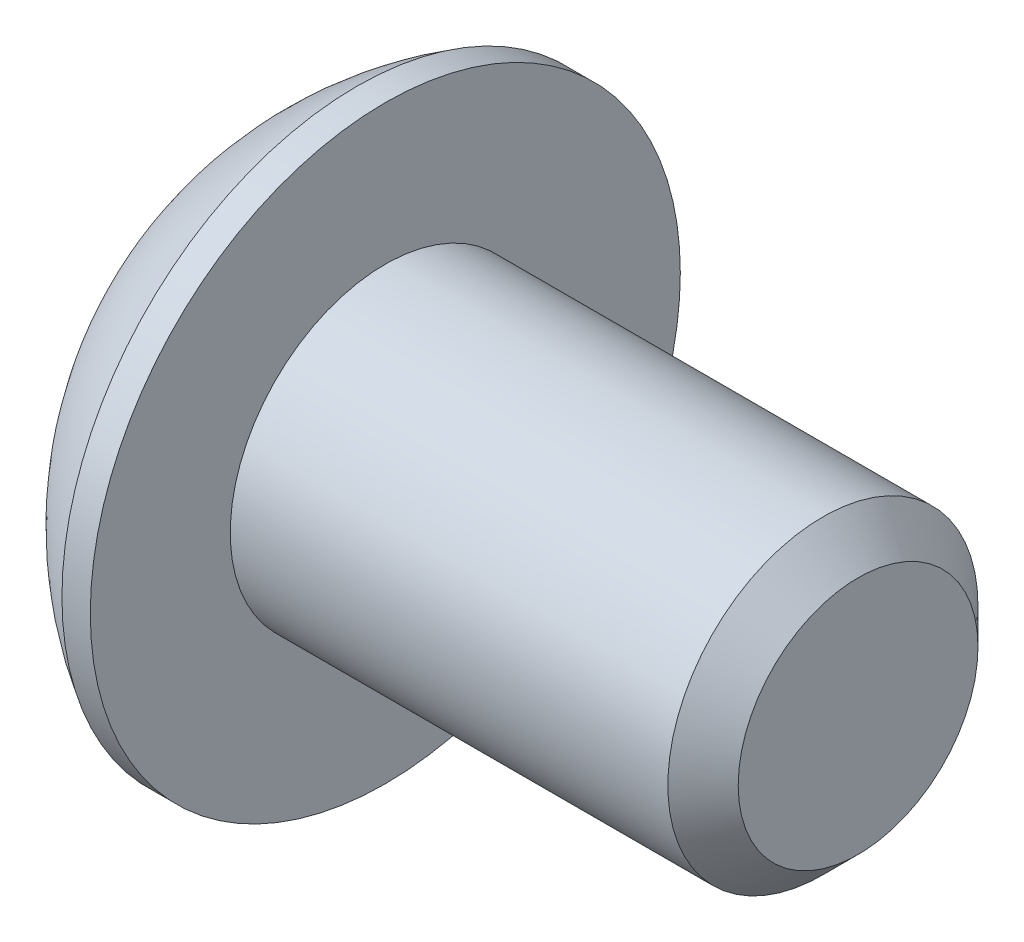
SolidWorks part; units mm, degrees
material "Cast Carbon Steel"
ref_plane "Front Plane" through (0, 0, 0) normal (0, 0, 1) x (1, 0, 0)
ref_plane "Top Plane" through (0, 0, 0) normal (0, 1, 0) x (1, 0, 0)
ref_plane "Right Plane" through (0, 0, 0) normal (1, 0, 0) x (0, 0, -1)
sketch "Sketch1" plane through (0, 0, 0) normal (0, 0, 1) x (1, 0, 0)
  line L0 (4.2799, 0) -> (-4.2799, 0) construction
  line L1 (4.2799, 0) -> (-4.2799, 0)
  line L14 (4.2799, 0) -> (4.2799, 2.0828)
  line L16 (4.2799, 2.0828) -> (-2.0701, 2.0828)
  line L17 (-2.0701, 2.0828) -> (-2.0701, 3.9624)
  line L18 (-2.0701, 3.9624) -> (-2.4511, 3.9624)
  line L19 (-4.2799, 1.9812) -> (-4.2799, 0)
  arc A1 (-2.4511, 3.9624) -> (-4.2799, 1.9812) centre (-0.146, 0) ccw
  dimension "D1" = 4.5841
  dimension "D2" = 7.9248
  dimension "D3" = 4.1656
  dimension "D4" = 2.2098
  dimension "D5" = 6.35
  dimension "D6" = 0.381
  dimension "D7" = 1.9812
revolve "Revolve2" add sketch "Sketch1" angle 360 about L0
cosmetic thread "Cosmetic Thread1" parameters "D1"=5, "D2"=3
sketch "Sketch4" plane through (-4.2799, 0, 0) normal (-1, 0, 0) x (0, 0, 1)
  point P0 (0, 0)
sketch "Sketch9" plane through (-4.2799, 0, 0) normal (-1, 0, 0) x (0, 0, 1)
  line L0 (0, 1.3785) -> (1.1938, 0.6892)
  line L1 (1.1938, -0.6892) -> (0, -1.3785)
  line L2 (0, -1.3785) -> (-1.1938, -0.6892)
  line L3 (-1.1938, -0.6892) -> (-1.1938, 0.6892)
  line L4 (-1.1938, 0.6892) -> (0, 1.3785)
  line L5 (1.1938, 0.6892) -> (-1.1938, -0.6892) construction
  line L6 (1.1938, 0.6892) -> (1.1938, -0.6892)
  line L7 (-1.1938, 0.6892) -> (1.1938, -0.6892) construction
  line L8 (0, 1.3785) -> (0, -1.3785) construction
  point P7 (0, 0)
  dimension "D1" = 2.3876
extrude "Cut-Extrude1" cut sketch "Sketch9" against normal blind 1.3208
hole_wizard "Tapped Hole1" positions "3DSketch3" profile "Sketch5" tap size "M2.5x0.45" standard "JIS"
sketch3d "3DSketch3"
  point P0 (-4.2799, 0, 0)
sketch "Sketch5" plane through (-4.2799, 0, 0) normal (0, 1, 0) x (0, 0, 1)
  line L0 (0, 0) -> (0, 2.0094)
  line L1 (0, 2.0094) -> (1.194, 1.32)
  line L2 (1.194, 1.32) -> (1.194, 0)
  line L5 (1.194, 0) -> (0, 0)
  line L10 (0, 2.0094) -> (-1.194, 1.32) construction
  line L11 (0, -6.35) -> (0, 107.95) construction
  dimension "Tap Drill Dia." = 2.388
  dimension "Tap Drill Depth" = 1.32
  dimension "Drill Angle" = 120
chamfer "Chamfer1" distance 0.4724 angle 45 1 edges at (4.2799, 0, -2.0828)
ref_axis "Axis1" through (-5.3213, 0, 0) along (1, 0, 0)
